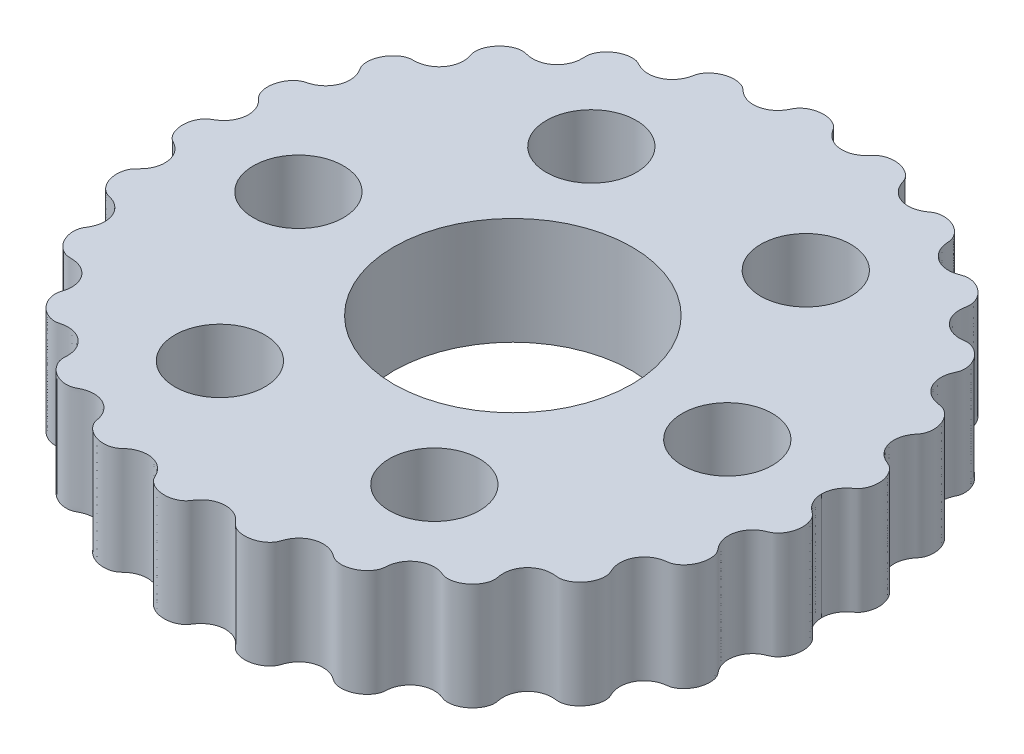
SolidWorks part; units mm, degrees
ref_plane "Front Plane" through (0, 0, 0) normal (0, 0, 1) x (1, 0, 0)
ref_plane "Top Plane" through (0, 0, 0) normal (0, 1, 0) x (1, 0, 0)
ref_plane "Right Plane" through (0, 0, 0) normal (1, 0, 0) x (0, 0, -1)
sketch "Sketch2" plane through (0, 0, 0) normal (0, 1, 0) x (1, 0, 0)
  line L0 (-15.4, 0) -> (14.4, 0) construction
  line L1 (0, 0) -> (0, 14.9128) construction
  line L2 (0, 0) -> (0, -14.9128) construction
  line L3 (0, 0) -> (-0.5, 0) construction
  line L4 (-0.5, 0) -> (-0.5, 15.3103) construction
  line L5 (-0.5, 0) -> (-0.5, -15.3103) construction
  line L6 (14.4, 0) -> (15.5, 0) construction
  line L7 (0, 0) -> (10, 0) construction
  line L8 (7.9, 0) -> (9.5, 0)
  line L9 (-0.5, 0) -> (9.5, 0) construction
  circle A0 centre (-0.5, 0) radius 16
  circle A1 centre (15.5, 0) radius 1
  circle A2 centre (15.0351, -3.8291) radius 1
  circle A3 centre (13.6673, -7.4356) radius 1
  circle A4 centre (11.4762, -10.61) radius 1
  circle A5 centre (8.589, -13.1677) radius 1
  circle A6 centre (5.1737, -14.9603) radius 1
  circle A7 centre (1.4286, -15.8833) radius 1
  circle A8 centre (-2.4286, -15.8833) radius 1
  circle A9 centre (-6.1737, -14.9603) radius 1
  circle A10 centre (-9.589, -13.1677) radius 1
  circle A11 centre (-12.4762, -10.61) radius 1
  circle A12 centre (-14.6673, -7.4356) radius 1
  circle A13 centre (-16.0351, -3.8291) radius 1
  circle A14 centre (-16.5, 0) radius 1
  circle A15 centre (-16.0351, 3.8291) radius 1
  circle A16 centre (-14.6673, 7.4356) radius 1
  circle A17 centre (-12.4762, 10.61) radius 1
  circle A18 centre (-9.589, 13.1677) radius 1
  circle A19 centre (-6.1737, 14.9603) radius 1
  circle A20 centre (-2.4286, 15.8833) radius 1
  circle A21 centre (1.4286, 15.8833) radius 1
  circle A22 centre (5.1737, 14.9603) radius 1
  circle A23 centre (8.589, 13.1677) radius 1
  circle A24 centre (11.4762, 10.61) radius 1
  circle A25 centre (13.6673, 7.4356) radius 1
  circle A26 centre (15.0351, 3.8291) radius 1
  circle A27 centre (0, 0) radius 10
  circle A28 centre (10, 0) radius 2.1
  circle A29 centre (5, -8.6603) radius 2.1
  circle A30 centre (-5, -8.6603) radius 2.1
  circle A31 centre (-10, 0) radius 2.1
  circle A32 centre (-5, 8.6603) radius 2.1
  circle A33 centre (5, 8.6603) radius 2.1
  circle A34 centre (-6, 8.6603) radius 2.1
  circle A35 centre (4, 8.6603) radius 2.1
  circle A36 centre (9, 0) radius 2.1
  circle A37 centre (4, -8.6603) radius 2.1
  circle A38 centre (-6, -8.6603) radius 2.1
  circle A39 centre (-1, 0) radius 10
  circle A40 centre (-11, 0) radius 2.1
  circle A41 centre (9.5, 0) radius 1.5
  circle A42 centre (4.5, -8.6603) radius 1.5
  circle A43 centre (-5.5, -8.6603) radius 1.5
  circle A44 centre (-10.5, 0) radius 1.5
  circle A45 centre (-5.5, 8.6603) radius 1.5
  circle A46 centre (4.5, 8.6603) radius 1.5
  circle A47 centre (0, 0) radius 5.55
  spline S0 degree 4 poles (14.1521, 3.1658) (14.188, 3.1199) (14.2658, 3.0332) (14.3775, 2.9384) (14.515, 2.8555) (14.6203, 2.806) (14.6874, 2.778) (14.7412, 2.7556) (14.7939, 2.7309) (14.8442, 2.7016) (14.9616, 2.6171) (15.116, 2.4418) (15.2531, 2.163) (15.3044, 1.8261) (15.2781, 1.5454) (15.2134, 1.3341) (15.1457, 1.199) (15.0717, 1.0959) (14.999, 1.0246) (14.9346, 0.9749) (14.8529, 0.9144) (14.7598, 0.8351) (14.6613, 0.7318) (14.5658, 0.5985) (14.4899, 0.4547) (14.4445, 0.3242) (14.4198, 0.2202) (14.4058, 0.1237) (14.3997, 0.036) (14.399, -0.0233) (14.4055, -0.1232) (14.4175, -0.2057) (14.4353, -0.2848) (14.4589, -0.3638) (14.4955, -0.4601) (14.5538, -0.5777) (14.629, -0.6905) (14.7205, -0.7952) (14.8099, -0.8785) (14.886, -0.9397) (14.9653, -0.9969) (15.0394, -1.0608) (15.1018, -1.1365) (15.1543, -1.2193) (15.2086, -1.3292) (15.2563, -1.4688) (15.2881, -1.6381) (15.2945, -1.881) (15.2523, -2.1199) (15.1638, -2.3444) (15.0424, -2.5231) (14.9425, -2.6287) (14.8453, -2.7036) (14.7572, -2.7504) (14.6644, -2.7867) (14.5734, -2.827) (14.4636, -2.8857) (14.309, -2.9902) (14.1305, -3.1658) (13.9721, -3.435) (13.894, -3.7733) (13.9169, -4.0803) (13.9952, -4.3102) (14.0824, -4.4685) (14.1503, -4.5677) (14.21, -4.6429) (14.2706, -4.7176) (14.3202, -4.8002) (14.3654, -4.9109) (14.3993, -5.0496) (14.4169, -5.2624) (14.3843, -5.5009) (14.3041, -5.731) (14.178, -5.9418) (14.0479, -6.0957) (13.9108, -6.2086) (13.7771, -6.2844) (13.6546, -6.3259) (13.5506, -6.3413) (13.4467, -6.3556) (13.3441, -6.3782) (13.2186, -6.4164) (13.0491, -6.4902) (12.8504, -6.6239) (12.6494, -6.8484) (12.5061, -7.1523) (12.463, -7.451) (12.49, -7.6921) (12.5392, -7.8624) (12.5803, -7.968) (12.6183, -8.0504) (12.6544, -8.1336) (12.6783, -8.2214) (12.6929, -8.336) (12.6907, -8.4762) (12.6543, -8.6855) (12.5452, -8.9512) (12.3731, -9.1837) (12.1492, -9.3663) (11.9533, -9.4633) (11.8116, -9.5062) (11.6867, -9.5225) (11.5835, -9.517) (11.4812, -9.5034) (11.3782, -9.4969) (11.2749, -9.4982) (11.1721, -9.508) (11.0085, -9.5382) (10.791, -9.6158) (10.5438, -9.7787) (10.3474, -10.0243) (10.2402, -10.2686) (10.1943, -10.4842) (10.1853, -10.6384) (10.1931, -10.7705) (10.2091, -10.8795) (10.2256, -10.9662) (10.236, -11.0539) (10.2331, -11.1423) (10.2158, -11.2534) (10.1767, -11.3842) (10.0886, -11.5718) (9.9146, -11.8006) (9.6439, -12.0158) (9.3384, -12.1314) (9.0923, -12.1519) (8.9388, -12.1247) (8.8741, -12.1049) (8.8233, -12.0863) (8.76, -12.0622) (8.6577, -12.0268) (8.5127, -11.9913) (8.2954, -11.971) (8.0233, -12.0058) (7.7397, -12.12) (7.4775, -12.3303) (7.3093, -12.5758) (7.2277, -12.7964) (7.1948, -12.9647) (7.1831, -13.0729) (7.1774, -13.16) (7.1639, -13.2682) (7.1207, -13.3961) (7.0432, -13.5357) (6.8963, -13.7154) (6.6678, -13.8963) (6.3478, -14.0387) (6.02, -14.0727) (5.7619, -14.0269) (5.5985, -13.9438) (5.5126, -13.8801) (5.4018, -13.8057) (5.2599, -13.7303) (5.0524, -13.6565) (4.7738, -13.623) (4.4626, -13.6683) (4.1888, -13.7999) (3.9912, -13.9665) (3.8578, -14.1339) (3.7826, -14.2632) (3.7309, -14.3799) (3.6959, -14.48) (3.6689, -14.5606) (3.6251, -14.6573) (3.5494, -14.7647) (3.44, -14.8752) (3.2557, -15.006) (2.9928, -15.1201) (2.6515, -15.1757) (2.3406, -15.1291) (2.1258, -15.0338) (2.011, -14.9468) (1.9698, -14.909) (1.9317, -14.8681) (1.8954, -14.8255) (1.8499, -14.7726) (1.7735, -14.691) (1.6576, -14.5893) (1.4677, -14.4687) (1.2013, -14.3748) (0.8943, -14.3518) (0.5705, -14.4236) (0.3173, -14.5632) (0.1515, -14.7141) (0.0481, -14.8418) (-0.0114, -14.9289) (-0.057, -15) (-0.1205, -15.0845) (-0.2167, -15.1711) (-0.3455, -15.2521) (-0.5484, -15.3356) (-0.8128, -15.3854) (-1.084, -15.3726) (-1.345, -15.2972) (-1.5435, -15.1922) (-1.6658, -15.0976) (-1.7547, -15.002) (-1.8112, -14.9128) (-1.8483, -14.8369) (-1.8948, -14.7422) (-1.9811, -14.5964) (-2.1305, -14.4153) (-2.3717, -14.2374) (-2.6941, -14.1243) (-3.0058, -14.1121) (-3.2798, -14.1742) (-3.4814, -14.2713) (-3.6077, -14.3581) (-3.6929, -14.4296) (-3.7443, -14.4763) (-3.7855, -14.5136) (-3.839, -14.5578) (-3.9718, -14.6426) (-4.2092, -14.7163) (-4.5379, -14.7232) (-4.871, -14.6233) (-5.1192, -14.4741) (-5.2872, -14.3161) (-5.3818, -14.1887) (-5.4416, -14.0686) (-5.4698, -13.9639) (-5.4862, -13.8788) (-5.5106, -13.7734) (-5.5628, -13.6112) (-5.6686, -13.4029) (-5.8615, -13.1808) (-6.1409, -13.0036) (-6.4324, -12.9205) (-6.707, -12.9139) (-6.9246, -12.958) (-7.0705, -13.0119) (-7.1719, -13.0612) (-7.2342, -13.0943) (-7.2842, -13.1203) (-7.3485, -13.1494) (-7.4504, -13.1813) (-7.5929, -13.1993) (-7.8225, -13.1875) (-8.1082, -13.1019) (-8.3607, -12.9481) (-8.5641, -12.7393) (-8.6869, -12.541) (-8.7459, -12.3913) (-8.7711, -12.2579) (-8.7697, -12.1482) (-8.7645, -12.0606) (-8.7633, -11.951) (-8.7731, -11.8212) (-8.8019, -11.6732) (-8.8729, -11.4717) (-9.0045, -11.25) (-9.2205, -11.0351) (-9.4997, -10.8905) (-9.7475, -10.8369) (-9.9383, -10.8322) (-10.0675, -10.8437) (-10.1698, -10.8609) (-10.2704, -10.8859) (-10.3717, -10.9089) (-10.4995, -10.9144) (-10.6499, -10.893) (-10.8644, -10.8236) (-11.1154, -10.6702) (-11.3185, -10.4608) (-11.4614, -10.2119) (-11.5248, -10.0134) (-11.5464, -9.8777) (-11.5487, -9.7646) (-11.5393, -9.6761) (-11.5169, -9.5902) (-11.4896, -9.5058) (-11.4606, -9.3988) (-11.4371, -9.2678) (-11.428, -9.1126) (-11.4489, -8.8917) (-11.5253, -8.6444) (-11.6806, -8.3917) (-11.9083, -8.1893) (-12.1461, -8.0664) (-12.3515, -8.0112) (-12.509, -7.9918) (-12.6408, -7.9895) (-12.7466, -7.9882) (-12.8744, -7.9638) (-13.0178, -7.9059) (-13.1692, -7.8114) (-13.319, -7.6747) (-13.472, -7.4805) (-13.5815, -7.2609) (-13.644, -7.0266) (-13.6529, -6.8129) (-13.6365, -6.6728) (-13.6064, -6.5605) (-13.5704, -6.4764) (-13.5232, -6.3982) (-13.4752, -6.3206) (-13.4215, -6.2199) (-13.3522, -6.0556) (-13.2972, -5.8178) (-13.3061, -5.5112) (-13.4183, -5.1858) (-13.5996, -4.9373) (-13.7884, -4.7826) (-13.9504, -4.6931) (-14.068, -4.6441) (-14.1647, -4.6121) (-14.2634, -4.587) (-14.3606, -4.5562) (-14.4721, -4.4972) (-14.5906, -4.4054) (-14.7415, -4.2409) (-14.8856, -3.984) (-14.9605, -3.7) (-14.9625, -3.4094) (-14.9171, -3.1994) (-14.8649, -3.0655) (-14.8048, -2.9613) (-14.7437, -2.886) (-14.6735, -2.8194) (-14.6048, -2.7515) (-14.5411, -2.6786) (-14.4829, -2.6013) (-14.3984, -2.4684) (-14.3099, -2.2678) (-14.2572, -1.9916) (-14.2948, -1.6527) (-14.4157, -1.3725) (-14.5648, -1.1806) (-14.7009, -1.0585) (-14.8015, -0.9857) (-14.886, -0.9336) (-14.9732, -0.8861) (-15.056, -0.8309) (-15.1453, -0.7457) (-15.2341, -0.6279) (-15.3021, -0.4979) (-15.3506, -0.3595) (-15.3784, -0.2422) (-15.3932, -0.1473) (-15.4005, -0.0379) (-15.4007, 0.0312) (-15.3943, 0.133) (-15.3819, 0.2227) (-15.3632, 0.3082) (-15.3383, 0.3938) (-15.2991, 0.498) (-15.241, 0.614) (-15.1569, 0.7356) (-15.0521, 0.8388) (-14.947, 0.9) (-14.8417, 0.9596) (-14.7374, 1.0292) (-14.6222, 1.1253) (-14.4762, 1.2888) (-14.3483, 1.5104) (-14.2696, 1.788) (-14.2718, 2.0824) (-14.3338, 2.3297) (-14.4228, 2.5131) (-14.5089, 2.6398) (-14.5912, 2.7371) (-14.6628, 2.8095) (-14.7315, 2.8736) (-14.7874, 2.9388) (-14.8392, 3.0187) (-14.9, 3.1445) (-14.933, 3.2628) (-14.9484, 3.3663) (-14.9531, 3.4358) knots 0 0 0 0 0 0.003662 0.007324 0.009155 0.010071 0.010986 0.011902 0.012818 0.013733 0.014649 0.020984 0.02732 0.032959 0.035778 0.038598 0.041156 0.042436 0.043715 0.044995 0.046274 0.048833 0.051398 0.053964 0.05653 0.059096 0.059963 0.060831 0.062566 0.06386 0.065154 0.066448 0.067743 0.069037 0.070331 0.072919 0.075992 0.077529 0.079065 0.080602 0.082139 0.083675 0.085212 0.086754 0.088296 0.09138 0.094464 0.097548 0.103529 0.106519 0.10951 0.111075 0.112641 0.114207 0.115773 0.117339 0.118905 0.122036 0.127492 0.132948 0.138255 0.143562 0.146585 0.148096 0.149608 0.151119 0.15263 0.154142 0.155653 0.158618 0.161583 0.167513 0.170668 0.173824 0.176979 0.180135 0.181785 0.183435 0.185086 0.186736 0.188387 0.190037 0.193338 0.198334 0.203329 0.208757 0.214186 0.217039 0.218465 0.219892 0.221319 0.222745 0.224172 0.225598 0.228568 0.231538 0.237477 0.243509 0.246525 0.249541 0.251164 0.252787 0.25441 0.256033 0.257656 0.259279 0.260902 0.262525 0.268116 0.273708 0.279232 0.281995 0.284757 0.287531 0.288919 0.290306 0.291693 0.293081 0.294468 0.295855 0.298752 0.301648 0.307441 0.313806 0.320171 0.321875 0.322726 0.323578 0.32443 0.325282 0.326985 0.330392 0.333799 0.338942 0.344084 0.349371 0.354658 0.3574 0.358771 0.360142 0.361513 0.362884 0.365627 0.368572 0.371516 0.377406 0.383828 0.390249 0.39193 0.393611 0.395291 0.396972 0.400333 0.403695 0.409076 0.414457 0.419833 0.422521 0.425209 0.427878 0.429213 0.430548 0.431883 0.433218 0.435887 0.438758 0.441629 0.44737 0.453781 0.460191 0.46107 0.46195 0.462829 0.463708 0.464587 0.465466 0.467225 0.470742 0.474259 0.479542 0.484825 0.489836 0.494847 0.497504 0.498832 0.500161 0.501489 0.502818 0.505475 0.508247 0.51102 0.516564 0.52227 0.525123 0.527976 0.530631 0.531959 0.533286 0.534614 0.535941 0.538597 0.543936 0.549276 0.554531 0.559787 0.563284 0.566782 0.568531 0.569405 0.570279 0.571154 0.572028 0.573777 0.580153 0.586529 0.592383 0.595311 0.598238 0.600963 0.602326 0.603688 0.605051 0.606414 0.609139 0.614393 0.619646 0.62466 0.629675 0.633224 0.636772 0.638547 0.639434 0.640321 0.641208 0.642095 0.64387 0.647026 0.650182 0.656494 0.66242 0.665383 0.668345 0.671105 0.672484 0.673864 0.675243 0.676623 0.679382 0.682041 0.684701 0.690021 0.695473 0.700926 0.704188 0.705819 0.70745 0.709081 0.710712 0.712344 0.713975 0.717095 0.720216 0.726458 0.732287 0.735201 0.738116 0.739511 0.740907 0.742302 0.743698 0.745093 0.746488 0.749279 0.752059 0.754839 0.760398 0.765424 0.770449 0.773769 0.777088 0.778748 0.780408 0.782068 0.783727 0.786901 0.790075 0.793249 0.796422 0.802397 0.805385 0.808372 0.809808 0.811244 0.812679 0.814115 0.81555 0.816986 0.819857 0.825318 0.830779 0.83599 0.841201 0.844404 0.846006 0.847607 0.849209 0.850811 0.852412 0.854014 0.857107 0.8602 0.866387 0.872353 0.875336 0.878319 0.87984 0.881361 0.882882 0.884402 0.885923 0.887444 0.888965 0.890486 0.895823 0.90116 0.906397 0.911634 0.914757 0.916319 0.91788 0.919441 0.921003 0.922564 0.924126 0.927182 0.930238 0.931767 0.933295 0.934823 0.936351 0.937751 0.93915 0.940549 0.941949 0.943348 0.944747 0.947546 0.950087 0.952628 0.953898 0.955168 0.957709 0.960509 0.96331 0.96891 0.973663 0.978415 0.981621 0.984826 0.986428 0.988031 0.989634 0.991236 0.992332 0.993427 0.995618 1 1 1 1 1 construction
  spline S1 degree 4 poles (14.4, 0) (14.4, -0.018) (14.401, -0.0542) (14.4055, -0.1232) (14.4175, -0.2057) (14.4353, -0.2848) (14.4589, -0.3638) (14.4955, -0.4601) (14.5538, -0.5777) (14.629, -0.6905) (14.7205, -0.7952) (14.8099, -0.8785) (14.886, -0.9397) (14.9653, -0.9969) (15.0394, -1.0608) (15.1018, -1.1365) (15.1543, -1.2193) (15.2086, -1.3292) (15.2563, -1.4688) (15.2881, -1.6381) (15.2945, -1.881) (15.2523, -2.1199) (15.1638, -2.3444) (15.0424, -2.5231) (14.9425, -2.6287) (14.8453, -2.7036) (14.7572, -2.7504) (14.6644, -2.7867) (14.5734, -2.827) (14.4636, -2.8857) (14.309, -2.9902) (14.1305, -3.1658) (13.9721, -3.435) (13.894, -3.7733) (13.9169, -4.0803) (13.9952, -4.3102) (14.0824, -4.4685) (14.1503, -4.5677) (14.21, -4.6429) (14.2706, -4.7176) (14.3202, -4.8002) (14.3654, -4.9109) (14.3993, -5.0496) (14.4169, -5.2624) (14.3843, -5.5009) (14.3041, -5.731) (14.178, -5.9418) (14.0479, -6.0957) (13.9108, -6.2086) (13.7771, -6.2844) (13.6546, -6.3259) (13.5506, -6.3413) (13.4467, -6.3556) (13.3441, -6.3782) (13.2186, -6.4164) (13.0491, -6.4902) (12.8504, -6.6239) (12.6494, -6.8484) (12.5061, -7.1523) (12.463, -7.451) (12.49, -7.6921) (12.5392, -7.8624) (12.5803, -7.968) (12.6183, -8.0504) (12.6544, -8.1336) (12.6783, -8.2214) (12.6929, -8.336) (12.6907, -8.4762) (12.6543, -8.6855) (12.5452, -8.9512) (12.3731, -9.1837) (12.1492, -9.3663) (11.9533, -9.4633) (11.8116, -9.5062) (11.6867, -9.5225) (11.5835, -9.517) (11.4812, -9.5034) (11.3782, -9.4969) (11.2749, -9.4982) (11.1721, -9.508) (11.0085, -9.5382) (10.791, -9.6158) (10.5438, -9.7787) (10.3474, -10.0243) (10.2402, -10.2686) (10.1943, -10.4842) (10.1853, -10.6384) (10.1931, -10.7705) (10.2091, -10.8795) (10.2256, -10.9662) (10.236, -11.0539) (10.2331, -11.1423) (10.2158, -11.2534) (10.1767, -11.3842) (10.0886, -11.5718) (9.9146, -11.8006) (9.6439, -12.0158) (9.3384, -12.1314) (9.0923, -12.1519) (8.9388, -12.1247) (8.8741, -12.1049) (8.8233, -12.0863) (8.76, -12.0622) (8.6577, -12.0268) (8.5127, -11.9913) (8.2954, -11.971) (8.0233, -12.0058) (7.7397, -12.12) (7.4775, -12.3303) (7.3093, -12.5758) (7.2277, -12.7964) (7.1948, -12.9647) (7.1831, -13.0729) (7.1774, -13.16) (7.1639, -13.2682) (7.1207, -13.3961) (7.0432, -13.5357) (6.8963, -13.7154) (6.6678, -13.8963) (6.3478, -14.0387) (6.02, -14.0727) (5.7619, -14.0269) (5.5985, -13.9438) (5.5126, -13.8801) (5.4018, -13.8057) (5.2599, -13.7303) (5.0524, -13.6565) (4.7738, -13.623) (4.4626, -13.6683) (4.1888, -13.7999) (3.9912, -13.9665) (3.8578, -14.1339) (3.7826, -14.2632) (3.7309, -14.3799) (3.6959, -14.48) (3.6689, -14.5606) (3.6251, -14.6573) (3.5494, -14.7647) (3.44, -14.8752) (3.2557, -15.006) (2.9928, -15.1201) (2.6515, -15.1757) (2.3406, -15.1291) (2.1258, -15.0338) (2.011, -14.9468) (1.9698, -14.909) (1.9317, -14.8681) (1.8954, -14.8255) (1.8499, -14.7726) (1.7735, -14.691) (1.6576, -14.5893) (1.4677, -14.4687) (1.2013, -14.3748) (0.8943, -14.3518) (0.5705, -14.4236) (0.3173, -14.5632) (0.1515, -14.7141) (0.0481, -14.8418) (-0.0114, -14.9289) (-0.057, -15) (-0.1205, -15.0845) (-0.2167, -15.1711) (-0.3455, -15.2521) (-0.5484, -15.3356) (-0.8128, -15.3854) (-1.084, -15.3726) (-1.345, -15.2972) (-1.5435, -15.1922) (-1.6658, -15.0976) (-1.7547, -15.002) (-1.8112, -14.9128) (-1.8483, -14.8369) (-1.8948, -14.7422) (-1.9811, -14.5964) (-2.1305, -14.4153) (-2.3717, -14.2374) (-2.6941, -14.1243) (-3.0058, -14.1121) (-3.2798, -14.1742) (-3.4814, -14.2713) (-3.6077, -14.3581) (-3.6929, -14.4296) (-3.7443, -14.4763) (-3.7855, -14.5136) (-3.839, -14.5578) (-3.9718, -14.6426) (-4.2092, -14.7163) (-4.5379, -14.7232) (-4.871, -14.6233) (-5.1192, -14.4741) (-5.2872, -14.3161) (-5.3818, -14.1887) (-5.4416, -14.0686) (-5.4698, -13.9639) (-5.4862, -13.8788) (-5.5106, -13.7734) (-5.5628, -13.6112) (-5.6686, -13.4029) (-5.8615, -13.1808) (-6.1409, -13.0036) (-6.4324, -12.9205) (-6.707, -12.9139) (-6.9246, -12.958) (-7.0705, -13.0119) (-7.1719, -13.0612) (-7.2342, -13.0943) (-7.2842, -13.1203) (-7.3485, -13.1494) (-7.4504, -13.1813) (-7.5929, -13.1993) (-7.8225, -13.1875) (-8.1082, -13.1019) (-8.3607, -12.9481) (-8.5641, -12.7393) (-8.6869, -12.541) (-8.7459, -12.3913) (-8.7711, -12.2579) (-8.7697, -12.1482) (-8.7645, -12.0606) (-8.7633, -11.951) (-8.7731, -11.8212) (-8.8019, -11.6732) (-8.8729, -11.4717) (-9.0045, -11.25) (-9.2205, -11.0351) (-9.4997, -10.8905) (-9.7475, -10.8369) (-9.9383, -10.8322) (-10.0675, -10.8437) (-10.1698, -10.8609) (-10.2704, -10.8859) (-10.3717, -10.9089) (-10.4995, -10.9144) (-10.6499, -10.893) (-10.8644, -10.8236) (-11.1154, -10.6702) (-11.3185, -10.4608) (-11.4614, -10.2119) (-11.5248, -10.0134) (-11.5464, -9.8777) (-11.5487, -9.7646) (-11.5393, -9.6761) (-11.5169, -9.5902) (-11.4896, -9.5058) (-11.4606, -9.3988) (-11.4371, -9.2678) (-11.428, -9.1126) (-11.4489, -8.8917) (-11.5253, -8.6444) (-11.6806, -8.3917) (-11.9083, -8.1893) (-12.1461, -8.0664) (-12.3515, -8.0112) (-12.509, -7.9918) (-12.6408, -7.9895) (-12.7466, -7.9882) (-12.8744, -7.9638) (-13.0178, -7.9059) (-13.1692, -7.8114) (-13.319, -7.6747) (-13.472, -7.4805) (-13.5815, -7.2609) (-13.644, -7.0266) (-13.6529, -6.8129) (-13.6365, -6.6728) (-13.6064, -6.5605) (-13.5704, -6.4764) (-13.5232, -6.3982) (-13.4752, -6.3206) (-13.4215, -6.2199) (-13.3522, -6.0556) (-13.2972, -5.8178) (-13.3061, -5.5112) (-13.4183, -5.1858) (-13.5996, -4.9373) (-13.7884, -4.7826) (-13.9504, -4.6931) (-14.068, -4.6441) (-14.1647, -4.6121) (-14.2634, -4.587) (-14.3606, -4.5562) (-14.4721, -4.4972) (-14.5906, -4.4054) (-14.7415, -4.2409) (-14.8856, -3.984) (-14.9605, -3.7) (-14.9625, -3.4094) (-14.9171, -3.1994) (-14.8649, -3.0655) (-14.8048, -2.9613) (-14.7437, -2.886) (-14.6735, -2.8194) (-14.6048, -2.7515) (-14.5411, -2.6786) (-14.4829, -2.6013) (-14.3984, -2.4684) (-14.3099, -2.2678) (-14.2572, -1.9916) (-14.2948, -1.6527) (-14.4157, -1.3725) (-14.5648, -1.1806) (-14.7009, -1.0585) (-14.8015, -0.9857) (-14.886, -0.9336) (-14.9732, -0.8861) (-15.056, -0.8309) (-15.1453, -0.7457) (-15.2341, -0.6279) (-15.3021, -0.4979) (-15.3506, -0.3595) (-15.3784, -0.2422) (-15.3932, -0.1473) (-15.3988, -0.0635) (-15.4, -0.0212) (-15.4, 0) knots 0.062566 0.062566 0.062566 0.062566 0.062566 0.06386 0.065154 0.066448 0.067743 0.069037 0.070331 0.072919 0.075992 0.077529 0.079065 0.080602 0.082139 0.083675 0.085212 0.086754 0.088296 0.09138 0.094464 0.097548 0.103529 0.106519 0.10951 0.111075 0.112641 0.114207 0.115773 0.117339 0.118905 0.122036 0.127492 0.132948 0.138255 0.143562 0.146585 0.148096 0.149608 0.151119 0.15263 0.154142 0.155653 0.158618 0.161583 0.167513 0.170668 0.173824 0.176979 0.180135 0.181785 0.183435 0.185086 0.186736 0.188387 0.190037 0.193338 0.198334 0.203329 0.208757 0.214186 0.217039 0.218465 0.219892 0.221319 0.222745 0.224172 0.225598 0.228568 0.231538 0.237477 0.243509 0.246525 0.249541 0.251164 0.252787 0.25441 0.256033 0.257656 0.259279 0.260902 0.262525 0.268116 0.273708 0.279232 0.281995 0.284757 0.287531 0.288919 0.290306 0.291693 0.293081 0.294468 0.295855 0.298752 0.301648 0.307441 0.313806 0.320171 0.321875 0.322726 0.323578 0.32443 0.325282 0.326985 0.330392 0.333799 0.338942 0.344084 0.349371 0.354658 0.3574 0.358771 0.360142 0.361513 0.362884 0.365627 0.368572 0.371516 0.377406 0.383828 0.390249 0.39193 0.393611 0.395291 0.396972 0.400333 0.403695 0.409076 0.414457 0.419833 0.422521 0.425209 0.427878 0.429213 0.430548 0.431883 0.433218 0.435887 0.438758 0.441629 0.44737 0.453781 0.460191 0.46107 0.46195 0.462829 0.463708 0.464587 0.465466 0.467225 0.470742 0.474259 0.479542 0.484825 0.489836 0.494847 0.497504 0.498832 0.500161 0.501489 0.502818 0.505475 0.508247 0.51102 0.516564 0.52227 0.525123 0.527976 0.530631 0.531959 0.533286 0.534614 0.535941 0.538597 0.543936 0.549276 0.554531 0.559787 0.563284 0.566782 0.568531 0.569405 0.570279 0.571154 0.572028 0.573777 0.580153 0.586529 0.592383 0.595311 0.598238 0.600963 0.602326 0.603688 0.605051 0.606414 0.609139 0.614393 0.619646 0.62466 0.629675 0.633224 0.636772 0.638547 0.639434 0.640321 0.641208 0.642095 0.64387 0.647026 0.650182 0.656494 0.66242 0.665383 0.668345 0.671105 0.672484 0.673864 0.675243 0.676623 0.679382 0.682041 0.684701 0.690021 0.695473 0.700926 0.704188 0.705819 0.70745 0.709081 0.710712 0.712344 0.713975 0.717095 0.720216 0.726458 0.732287 0.735201 0.738116 0.739511 0.740907 0.742302 0.743698 0.745093 0.746488 0.749279 0.752059 0.754839 0.760398 0.765424 0.770449 0.773769 0.777088 0.778748 0.780408 0.782068 0.783727 0.786901 0.790075 0.793249 0.796422 0.802397 0.805385 0.808372 0.809808 0.811244 0.812679 0.814115 0.81555 0.816986 0.819857 0.825318 0.830779 0.83599 0.841201 0.844404 0.846006 0.847607 0.849209 0.850811 0.852412 0.854014 0.857107 0.8602 0.866387 0.872353 0.875336 0.878319 0.87984 0.881361 0.882882 0.884402 0.885923 0.887444 0.888965 0.890486 0.895823 0.90116 0.906397 0.911634 0.914757 0.916319 0.91788 0.919441 0.921003 0.922564 0.924126 0.927182 0.930238 0.931767 0.933295 0.934823 0.936351 0.936351 0.936351 0.936351 0.936351
  spline S2 degree 4 poles (14.4, 0) (14.4, 0.018) (14.401, 0.0542) (14.4055, 0.1232) (14.4175, 0.2057) (14.4353, 0.2848) (14.4589, 0.3638) (14.4955, 0.4601) (14.5538, 0.5777) (14.629, 0.6905) (14.7205, 0.7952) (14.8099, 0.8785) (14.886, 0.9397) (14.9653, 0.9969) (15.0394, 1.0608) (15.1018, 1.1365) (15.1543, 1.2193) (15.2086, 1.3292) (15.2563, 1.4688) (15.2881, 1.6381) (15.2945, 1.881) (15.2523, 2.1199) (15.1638, 2.3444) (15.0424, 2.5231) (14.9425, 2.6287) (14.8453, 2.7036) (14.7572, 2.7504) (14.6644, 2.7867) (14.5734, 2.827) (14.4636, 2.8857) (14.309, 2.9902) (14.1305, 3.1658) (13.9721, 3.435) (13.894, 3.7733) (13.9169, 4.0803) (13.9952, 4.3102) (14.0824, 4.4685) (14.1503, 4.5677) (14.21, 4.6429) (14.2706, 4.7176) (14.3202, 4.8002) (14.3654, 4.9109) (14.3993, 5.0496) (14.4169, 5.2624) (14.3843, 5.5009) (14.3041, 5.731) (14.178, 5.9418) (14.0479, 6.0957) (13.9108, 6.2086) (13.7771, 6.2844) (13.6546, 6.3259) (13.5506, 6.3413) (13.4467, 6.3556) (13.3441, 6.3782) (13.2186, 6.4164) (13.0491, 6.4902) (12.8504, 6.6239) (12.6494, 6.8484) (12.5061, 7.1523) (12.463, 7.451) (12.49, 7.6921) (12.5392, 7.8624) (12.5803, 7.968) (12.6183, 8.0504) (12.6544, 8.1336) (12.6783, 8.2214) (12.6929, 8.336) (12.6907, 8.4762) (12.6543, 8.6855) (12.5452, 8.9512) (12.3731, 9.1837) (12.1492, 9.3663) (11.9533, 9.4633) (11.8116, 9.5062) (11.6867, 9.5225) (11.5835, 9.517) (11.4812, 9.5034) (11.3782, 9.4969) (11.2749, 9.4982) (11.1721, 9.508) (11.0085, 9.5382) (10.791, 9.6158) (10.5438, 9.7787) (10.3474, 10.0243) (10.2402, 10.2686) (10.1943, 10.4842) (10.1853, 10.6384) (10.1931, 10.7705) (10.2091, 10.8795) (10.2256, 10.9662) (10.236, 11.0539) (10.2331, 11.1423) (10.2158, 11.2534) (10.1767, 11.3842) (10.0886, 11.5718) (9.9146, 11.8006) (9.6439, 12.0158) (9.3384, 12.1314) (9.0923, 12.1519) (8.9388, 12.1247) (8.8741, 12.1049) (8.8233, 12.0863) (8.76, 12.0622) (8.6577, 12.0268) (8.5127, 11.9913) (8.2954, 11.971) (8.0233, 12.0058) (7.7397, 12.12) (7.4775, 12.3303) (7.3093, 12.5758) (7.2277, 12.7964) (7.1948, 12.9647) (7.1831, 13.0729) (7.1774, 13.16) (7.1639, 13.2682) (7.1207, 13.3961) (7.0432, 13.5357) (6.8963, 13.7154) (6.6678, 13.8963) (6.3478, 14.0387) (6.02, 14.0727) (5.7619, 14.0269) (5.5985, 13.9438) (5.5126, 13.8801) (5.4018, 13.8057) (5.2599, 13.7303) (5.0524, 13.6565) (4.7738, 13.623) (4.4626, 13.6683) (4.1888, 13.7999) (3.9912, 13.9665) (3.8578, 14.1339) (3.7826, 14.2632) (3.7309, 14.3799) (3.6959, 14.48) (3.6689, 14.5606) (3.6251, 14.6573) (3.5494, 14.7647) (3.44, 14.8752) (3.2557, 15.006) (2.9928, 15.1201) (2.6515, 15.1757) (2.3406, 15.1291) (2.1258, 15.0338) (2.011, 14.9468) (1.9698, 14.909) (1.9317, 14.8681) (1.8954, 14.8255) (1.8499, 14.7726) (1.7735, 14.691) (1.6576, 14.5893) (1.4677, 14.4687) (1.2013, 14.3748) (0.8943, 14.3518) (0.5705, 14.4236) (0.3173, 14.5632) (0.1515, 14.7141) (0.0481, 14.8418) (-0.0114, 14.9289) (-0.057, 15) (-0.1205, 15.0845) (-0.2167, 15.1711) (-0.3455, 15.2521) (-0.5484, 15.3356) (-0.8128, 15.3854) (-1.084, 15.3726) (-1.345, 15.2972) (-1.5435, 15.1922) (-1.6658, 15.0976) (-1.7547, 15.002) (-1.8112, 14.9128) (-1.8483, 14.8369) (-1.8948, 14.7422) (-1.9811, 14.5964) (-2.1305, 14.4153) (-2.3717, 14.2374) (-2.6941, 14.1243) (-3.0058, 14.1121) (-3.2798, 14.1742) (-3.4814, 14.2713) (-3.6077, 14.3581) (-3.6929, 14.4296) (-3.7443, 14.4763) (-3.7855, 14.5136) (-3.839, 14.5578) (-3.9718, 14.6426) (-4.2092, 14.7163) (-4.5379, 14.7232) (-4.871, 14.6233) (-5.1192, 14.4741) (-5.2872, 14.3161) (-5.3818, 14.1887) (-5.4416, 14.0686) (-5.4698, 13.9639) (-5.4862, 13.8788) (-5.5106, 13.7734) (-5.5628, 13.6112) (-5.6686, 13.4029) (-5.8615, 13.1808) (-6.1409, 13.0036) (-6.4324, 12.9205) (-6.707, 12.9139) (-6.9246, 12.958) (-7.0705, 13.0119) (-7.1719, 13.0612) (-7.2342, 13.0943) (-7.2842, 13.1203) (-7.3485, 13.1494) (-7.4504, 13.1813) (-7.5929, 13.1993) (-7.8225, 13.1875) (-8.1082, 13.1019) (-8.3607, 12.9481) (-8.5641, 12.7393) (-8.6869, 12.541) (-8.7459, 12.3913) (-8.7711, 12.2579) (-8.7697, 12.1482) (-8.7645, 12.0606) (-8.7633, 11.951) (-8.7731, 11.8212) (-8.8019, 11.6732) (-8.8729, 11.4717) (-9.0045, 11.25) (-9.2205, 11.0351) (-9.4997, 10.8905) (-9.7475, 10.8369) (-9.9383, 10.8322) (-10.0675, 10.8437) (-10.1698, 10.8609) (-10.2704, 10.8859) (-10.3717, 10.9089) (-10.4995, 10.9144) (-10.6499, 10.893) (-10.8644, 10.8236) (-11.1154, 10.6702) (-11.3185, 10.4608) (-11.4614, 10.2119) (-11.5248, 10.0134) (-11.5464, 9.8777) (-11.5487, 9.7646) (-11.5393, 9.6761) (-11.5169, 9.5902) (-11.4896, 9.5058) (-11.4606, 9.3988) (-11.4371, 9.2678) (-11.428, 9.1126) (-11.4489, 8.8917) (-11.5253, 8.6444) (-11.6806, 8.3917) (-11.9083, 8.1893) (-12.1461, 8.0664) (-12.3515, 8.0112) (-12.509, 7.9918) (-12.6408, 7.9895) (-12.7466, 7.9882) (-12.8744, 7.9638) (-13.0178, 7.9059) (-13.1692, 7.8114) (-13.319, 7.6747) (-13.472, 7.4805) (-13.5815, 7.2609) (-13.644, 7.0266) (-13.6529, 6.8129) (-13.6365, 6.6728) (-13.6064, 6.5605) (-13.5704, 6.4764) (-13.5232, 6.3982) (-13.4752, 6.3206) (-13.4215, 6.2199) (-13.3522, 6.0556) (-13.2972, 5.8178) (-13.3061, 5.5112) (-13.4183, 5.1858) (-13.5996, 4.9373) (-13.7884, 4.7826) (-13.9504, 4.6931) (-14.068, 4.6441) (-14.1647, 4.6121) (-14.2634, 4.587) (-14.3606, 4.5562) (-14.4721, 4.4972) (-14.5906, 4.4054) (-14.7415, 4.2409) (-14.8856, 3.984) (-14.9605, 3.7) (-14.9625, 3.4094) (-14.9171, 3.1994) (-14.8649, 3.0655) (-14.8048, 2.9613) (-14.7437, 2.886) (-14.6735, 2.8194) (-14.6048, 2.7515) (-14.5411, 2.6786) (-14.4829, 2.6013) (-14.3984, 2.4684) (-14.3099, 2.2678) (-14.2572, 1.9916) (-14.2948, 1.6527) (-14.4157, 1.3725) (-14.5648, 1.1806) (-14.7009, 1.0585) (-14.8015, 0.9857) (-14.886, 0.9336) (-14.9732, 0.8861) (-15.056, 0.8309) (-15.1453, 0.7457) (-15.2341, 0.6279) (-15.3021, 0.4979) (-15.3506, 0.3595) (-15.3784, 0.2422) (-15.3932, 0.1473) (-15.3988, 0.0635) (-15.4, 0.0212) (-15.4, 0) knots 0.062566 0.062566 0.062566 0.062566 0.062566 0.06386 0.065154 0.066448 0.067743 0.069037 0.070331 0.072919 0.075992 0.077529 0.079065 0.080602 0.082139 0.083675 0.085212 0.086754 0.088296 0.09138 0.094464 0.097548 0.103529 0.106519 0.10951 0.111075 0.112641 0.114207 0.115773 0.117339 0.118905 0.122036 0.127492 0.132948 0.138255 0.143562 0.146585 0.148096 0.149608 0.151119 0.15263 0.154142 0.155653 0.158618 0.161583 0.167513 0.170668 0.173824 0.176979 0.180135 0.181785 0.183435 0.185086 0.186736 0.188387 0.190037 0.193338 0.198334 0.203329 0.208757 0.214186 0.217039 0.218465 0.219892 0.221319 0.222745 0.224172 0.225598 0.228568 0.231538 0.237477 0.243509 0.246525 0.249541 0.251164 0.252787 0.25441 0.256033 0.257656 0.259279 0.260902 0.262525 0.268116 0.273708 0.279232 0.281995 0.284757 0.287531 0.288919 0.290306 0.291693 0.293081 0.294468 0.295855 0.298752 0.301648 0.307441 0.313806 0.320171 0.321875 0.322726 0.323578 0.32443 0.325282 0.326985 0.330392 0.333799 0.338942 0.344084 0.349371 0.354658 0.3574 0.358771 0.360142 0.361513 0.362884 0.365627 0.368572 0.371516 0.377406 0.383828 0.390249 0.39193 0.393611 0.395291 0.396972 0.400333 0.403695 0.409076 0.414457 0.419833 0.422521 0.425209 0.427878 0.429213 0.430548 0.431883 0.433218 0.435887 0.438758 0.441629 0.44737 0.453781 0.460191 0.46107 0.46195 0.462829 0.463708 0.464587 0.465466 0.467225 0.470742 0.474259 0.479542 0.484825 0.489836 0.494847 0.497504 0.498832 0.500161 0.501489 0.502818 0.505475 0.508247 0.51102 0.516564 0.52227 0.525123 0.527976 0.530631 0.531959 0.533286 0.534614 0.535941 0.538597 0.543936 0.549276 0.554531 0.559787 0.563284 0.566782 0.568531 0.569405 0.570279 0.571154 0.572028 0.573777 0.580153 0.586529 0.592383 0.595311 0.598238 0.600963 0.602326 0.603688 0.605051 0.606414 0.609139 0.614393 0.619646 0.62466 0.629675 0.633224 0.636772 0.638547 0.639434 0.640321 0.641208 0.642095 0.64387 0.647026 0.650182 0.656494 0.66242 0.665383 0.668345 0.671105 0.672484 0.673864 0.675243 0.676623 0.679382 0.682041 0.684701 0.690021 0.695473 0.700926 0.704188 0.705819 0.70745 0.709081 0.710712 0.712344 0.713975 0.717095 0.720216 0.726458 0.732287 0.735201 0.738116 0.739511 0.740907 0.742302 0.743698 0.745093 0.746488 0.749279 0.752059 0.754839 0.760398 0.765424 0.770449 0.773769 0.777088 0.778748 0.780408 0.782068 0.783727 0.786901 0.790075 0.793249 0.796422 0.802397 0.805385 0.808372 0.809808 0.811244 0.812679 0.814115 0.81555 0.816986 0.819857 0.825318 0.830779 0.83599 0.841201 0.844404 0.846006 0.847607 0.849209 0.850811 0.852412 0.854014 0.857107 0.8602 0.866387 0.872353 0.875336 0.878319 0.87984 0.881361 0.882882 0.884402 0.885923 0.887444 0.888965 0.890486 0.895823 0.90116 0.906397 0.911634 0.914757 0.916319 0.91788 0.919441 0.921003 0.922564 0.924126 0.927182 0.930238 0.931767 0.933295 0.934823 0.936351 0.936351 0.936351 0.936351 0.936351
  dimension "D1" = 32
  dimension "D2" = 2
  dimension "D4" = 20
  dimension "D5" = 4.2
  dimension "D8" = 6
  dimension "D7" = 10
  dimension "D9" = 10
  dimension "D3" = 26
  dimension "D6" = 6
extrude "Boss-Extrude1" add sketch "Sketch2" along normal blind 5 contours S1 S2
sketch "Sketch3" plane through (0, 0, 0) normal (0, 1, 0) x (1, 0, 0)
  circle A0 centre (10, 0) radius 2.1
  circle A1 centre (5, -8.6603) radius 2.1
  circle A2 centre (-5, -8.6603) radius 2.1
  circle A3 centre (-10, 0) radius 2.1
  circle A4 centre (-5, 8.6603) radius 2.1
  circle A5 centre (5, 8.6603) radius 2.1
extrude "Cut-Extrude1" cut sketch "Sketch3" along normal through all
sketch "Sketch5" plane through (0, 0, 0) normal (0, 1, 0) x (1, 0, 0)
  circle A0 centre (0, 0) radius 5.55
extrude "Cut-Extrude2" cut sketch "Sketch5" along normal through all
